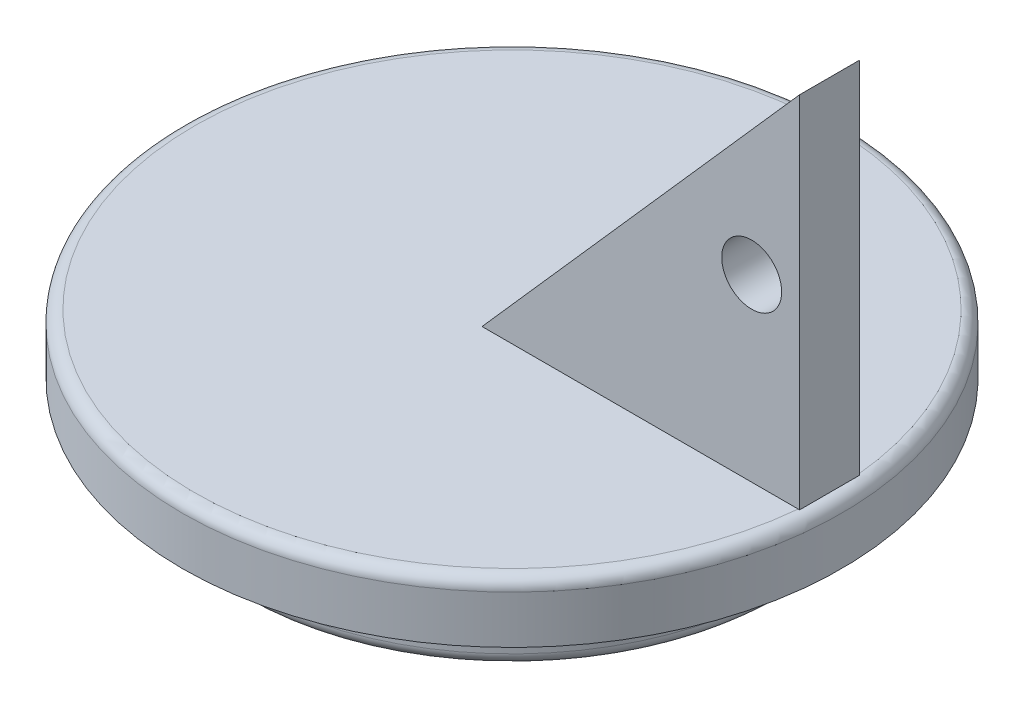
SolidWorks part; units mm, degrees
ref_plane "Front Plane" through (0, 0, 0) normal (0, 0, 1) x (1, 0, 0)
ref_plane "Top Plane" through (0, 0, 0) normal (0, 1, 0) x (1, 0, 0)
ref_plane "Right Plane" through (0, 0, 0) normal (1, 0, 0) x (0, 0, -1)
sketch "Sketch2" plane through (0, 0, 0) normal (0, 0, 1) x (1, 0, 0)
  line L0 (0, 0) -> (22.5, 0)
  line L1 (22.5, 0) -> (22.5, 5)
  line L2 (22.5, 5) -> (27.5, 5)
  line L3 (27.5, 5) -> (27.5, 10)
  line L4 (27.5, 10) -> (0, 10)
  line L5 (0, 10) -> (0, 0)
  dimension "D1" = 22.5
  dimension "D2" = 5
  dimension "D3" = 5
  dimension "D4" = 5
revolve "Revolve1" add sketch "Sketch2" angle 360 about L5
fillet "Fillet1" radius 1 3 edges at (0, 10, 27.5) (0, 5, 22.5) (0, 0, 22.5)
sketch "Sketch5" plane through (0, 0, 0) normal (0, 0, 1) x (1, 0, 0)
  line L0 (26.5, 10) -> (26.5, 40)
  line L1 (0, 10) -> (26.5, 40)
  line L2 (26.5, 10) -> (-26.5, 10) construction
  line L3 (0, 10) -> (26.5, 10)
  line L4 (26.5, 25) -> (22.5, 25) construction
  circle A0 centre (22.5, 25) radius 2.5
  dimension "D3" = 5
  dimension "D1" = 30
  dimension "D2" = 4
extrude "Boss-Extrude2" add sketch "Sketch5" along normal mid plane 5
